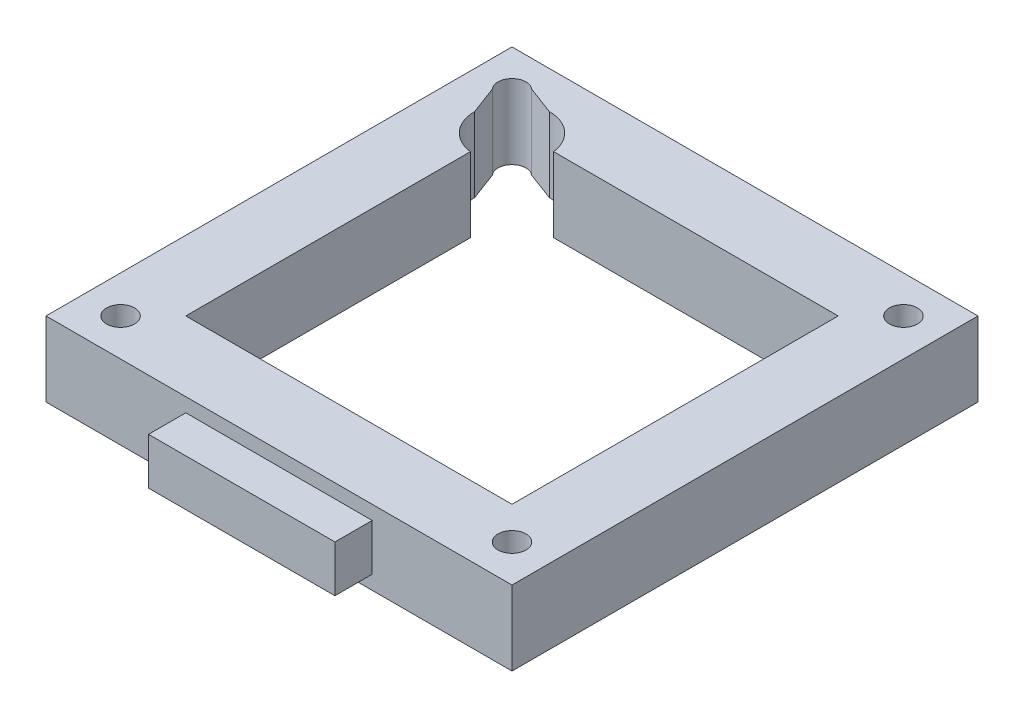
SolidWorks part; units mm, degrees
ref_plane "Front Plane" through (0, 0, 0) normal (0, 0, 1) x (1, 0, 0)
ref_plane "Top Plane" through (0, 0, 0) normal (0, 1, 0) x (1, 0, 0)
ref_plane "Right Plane" through (0, 0, 0) normal (1, 0, 0) x (0, 0, -1)
sketch "Sketch1" plane through (0, 0, 0) normal (0, 1, 0) x (1, 0, 0)
  line L0 (17.5, 17.5) -> (-13.0314, 17.5)
  line L1 (-25, -25) -> (25, -25)
  line L2 (-25, -25) -> (-25, 25)
  line L3 (-25, 25) -> (25, 25)
  line L4 (25, -25) -> (25, 25)
  line L5 (0, 25) -> (0, -25) construction
  line L6 (-25, 0) -> (25, 0) construction
  line L11 (0, 20) -> (0, -20) construction
  line L12 (-20, 0) -> (20, 0) construction
  line L13 (-17.5, -17.5) -> (17.5, -17.5)
  line L16 (17.5, -17.5) -> (17.5, 17.5)
  line L17 (0, 17.5) -> (0, -17.5) construction
  line L18 (-17.5, 0) -> (17.5, 0) construction
  line L19 (-17.5, -17.5) -> (-17.5, 13.0314)
  line L20 (-22.1301, 20.0137) -> (-21, 17)
  line L21 (-20.0137, 22.1301) -> (-17, 21)
  arc A0 (-20.0137, 22.1301) -> (-22.1301, 20.0137) centre (-21, 21) ccw
  circle A1 centre (21, 21) radius 1.5
  circle A2 centre (21, -21) radius 1.5
  circle A3 centre (-21, -21) radius 1.5
  arc A4 (-21, 17) -> (-17, 21) centre (-17, 17) ccw
  point P0 (0, 0)
  point P4 (0, 0)
  point P13 (0, 0)
  dimension "D1" = 50
  dimension "D2" = 50
  dimension "D4" = 35
extrude "Support" add sketch "Sketch1" along normal blind 8 contours L1 L4 L3 L2 A4 L0 L16 L13 L19 L20 A0 L21 A1 A2 A3 region at (-24.2929, 0, 0)
sketch "Sketch2" plane through (0, 0, 0) normal (0, 0, 1) x (1, 0, 0)
  line L4 (-10, 1.5) -> (10, 1.5)
  line L5 (-10, 1.5) -> (-10, 6.5)
  line L6 (-10, 6.5) -> (10, 6.5)
  line L7 (10, 1.5) -> (10, 6.5)
  line L8 (0, 6.5) -> (0, 1.5) construction
  line L9 (-10, 4) -> (10, 4) construction
  point P6 (0, 4)
  dimension "D1" = 20
  dimension "D2" = 5
extrude "South Dowel" add sketch "Sketch2" along normal blind 4 from surface starting at face at (0, 4, 25)
sketch "Sketch3" plane through (0, 0, 0) normal (1, 0, 0) x (0, 0, -1)
  line L4 (-10, 1.5) -> (10, 1.5)
  line L5 (-10, 1.5) -> (-10, 6.5)
  line L6 (-10, 6.5) -> (10, 6.5)
  line L7 (10, 1.5) -> (10, 6.5)
  line L8 (0, 6.5) -> (0, 1.5) construction
  line L9 (-10, 4) -> (10, 4) construction
  point P6 (0, 4)
  dimension "D1" = 20
  dimension "D2" = 5
extrude "West Cut" cut sketch "Sketch3" along normal blind 4 from surface starting at face at (-25, 4, 0)
